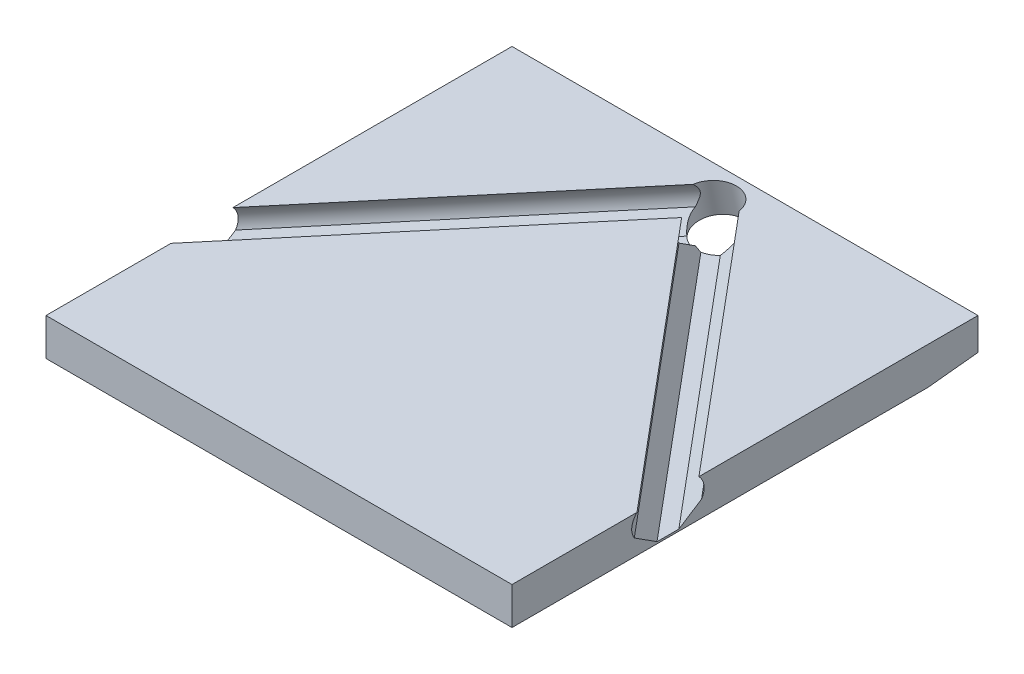
SolidWorks part; units mm, degrees
ref_plane "Front Plane" through (0, 0, 0) normal (0, 0, 1) x (1, 0, 0)
ref_plane "Top Plane" through (0, 0, 0) normal (0, 1, 0) x (1, 0, 0)
ref_plane "Right Plane" through (0, 0, 0) normal (1, 0, 0) x (0, 0, -1)
sketch "Sketch1" plane through (0, 0, 0) normal (0, 1, 0) x (1, 0, 0)
  line L1 (-125, -125) -> (125, -125)
  line L2 (-125, -125) -> (-125, 125)
  line L3 (-125, 125) -> (125, 125)
  line L4 (125, -125) -> (125, 125)
  line L5 (-125, -125) -> (125, 125) construction
  line L6 (-125, 125) -> (125, -125) construction
  point P0 (0, 0)
  dimension "D1" = 250
  dimension "D2" = 250
extrude "Boss-Extrude1" add sketch "Sketch1" along normal blind 20
sketch "Sketch2" plane through (125, 0, 0) normal (1, 0, 0) x (0, 0, -1)
  line L0 (125, 2.8223) -> (125, 0)
  line L1 (125, 20) -> (125, 0) construction
  line L2 (125, 0) -> (98.1479, 0)
  line L3 (-125, 0) -> (125, 0) construction
  line L4 (98.1479, 0) -> (125, 2.8223)
  point P5 (65.0658, 0)
  dimension "D1" = 6
  dimension "D2" = 27
extrude "Cut-Extrude1" cut sketch "Sketch2" against normal through all
ref_plane "Plane1" through (0, -19.9602, -4.2427) normal (0, -0.9781, -0.2079) x (1, 0, 0)
sketch "Sketch3" plane through (0, -20.1752, -3.2313) normal (0, -0.9781, -0.2079) x (1, 0, 0)
  line L0 (-125, -97.0371) -> (125, -123.8892) construction
  circle A0 centre (0, -110.4632) radius 12.5
  dimension "D1" = 25
extrude "Cut-Extrude2" cut sketch "Sketch3" against normal through all both and the other way through all
sketch "Sketch6" plane through (0, 20, 0) normal (0, 1, 0) x (1, 0, 0)
  line L0 (0, 120.402) -> (0, 94.8435) construction
  ellipse E0 centre (0, 107.6228) end of major axis (0, 120.402) minor radius 12.5 construction
  point P9 (0, 107.6228)
ref_axis "Axis1" through (0, -20.4098, -107.6228) along (0, 1, 0)
ref_plane "Plane2" through (52.9939, 0, -63.1556) normal (0.6428, 0, -0.766) x (0, 1, 0)
ref_plane "Plane3" through (-52.9939, 0, -63.1556) normal (0.6428, 0, 0.766) x (0, 1, 0)
sketch "Sketch4" plane through (56.7704, 0, -59.9868) normal (-0.6428, 0, 0.766) x (0.766, 0, 0.6428)
  line L0 (-61.4923, 20) -> (-86.7246, 20) construction
  line L1 (-20.337, 20) -> (171.1741, 20) construction
  line L2 (-20.337, 0) -> (171.1741, 0) construction
  line L3 (-20.337, 1) -> (171.1741, 1) construction
  line L4 (-20.337, 20) -> (-20.337, 0) construction
  line L5 (171.1741, 20) -> (171.1741, 0) construction
  line L6 (-84.7855, 20) -> (-63.4314, 20)
  line L7 (-85.7043, 8.8324) -> (-77.8719, 1)
  line L8 (-77.8719, 1) -> (-70.345, 1)
  line L9 (-70.345, 1) -> (-62.5126, 8.8324)
  line L10 (-61.4923, 20) -> (-86.7246, 20) construction
  line L11 (-74.1084, 20) -> (-74.1084, 0) construction
  line L15 (-20.337, 2) -> (171.1741, 2) construction
  circle A0 centre (-74.1084, 13.5) radius 12.5 construction
  circle A1 centre (-74.1084, 13.5) radius 11.5 construction
  arc A2 (-85.7043, 8.8324) -> (-84.7855, 20) centre (-74.1084, 13.5) cw
  arc A3 (-62.5126, 8.8324) -> (-63.4314, 20) centre (-74.1084, 13.5) ccw
  point P22 (0, 0)
  point P24 (0, 0)
  point P26 (-4.9299, 1)
  dimension "D1" = 25
  dimension "D8" = 23
  dimension "D2" = 1
  dimension "D4" = 1
  dimension "D5" = 45
  dimension "D6" = 45
extrude "Cut-Extrude3" cut sketch "Sketch4" along normal through all
sketch "Sketch9" plane through (-56.7704, 0, -59.9868) normal (-0.6428, 0, -0.766) x (-0.766, 0, 0.6428)
  line L1 (-63.4314, 20) -> (-84.7855, 20)
  line L2 (171.1741, 20) -> (-20.337, 20) construction
  line L3 (119.9888, 1) -> (171.1741, 1) construction
  line L7 (-85.7043, 8.8324) -> (-77.8719, 1)
  line L8 (-77.8719, 1) -> (-70.345, 1)
  line L9 (-70.345, 1) -> (-62.5126, 8.8324)
  line L11 (-74.1084, 20) -> (-74.1084, 0) construction
  line L15 (119.2126, 2) -> (171.1741, 2) construction
  line L16 (171.1741, 0) -> (-20.337, 0) construction
  circle A0 centre (-74.1084, 13.5) radius 12.5 construction
  circle A1 centre (-74.1084, 13.5) radius 11.5 construction
  arc A2 (-85.7043, 8.8324) -> (-84.7855, 20) centre (-74.1084, 13.5) cw
  arc A3 (-62.5126, 8.8324) -> (-63.4314, 20) centre (-74.1084, 13.5) ccw
  point P3 (-19.4084, 20)
  dimension "D1" = 25
  dimension "D8" = 23
  dimension "D2" = 1
  dimension "D3" = 1
  dimension "D5" = 45
  dimension "D6" = 45
extrude "Cut-Extrude5" cut sketch "Sketch9" against normal through all
